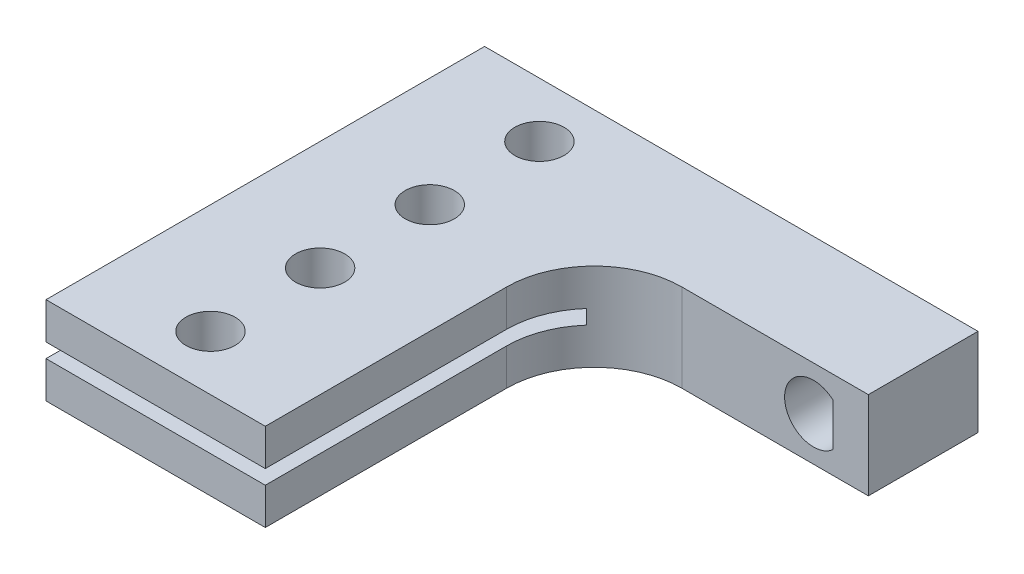
SolidWorks part; units mm, degrees
ref_plane "Front Plane" through (0, 0, 0) normal (0, 0, 1) x (1, 0, 0)
ref_plane "Top Plane" through (0, 0, 0) normal (0, 1, 0) x (1, 0, 0)
ref_plane "Right Plane" through (0, 0, 0) normal (1, 0, 0) x (0, 0, -1)
sketch "Sketch1" plane through (0, 0, 0) normal (0, 1, 0) x (1, 0, 0)
  line L0 (-33.097, 5.3879) -> (-20.397, 5.3879)
  line L2 (-20.397, 5.3879) -> (-4.522, 5.3879)
  line L3 (-4.522, 5.3879) -> (-4.522, -0.9621)
  line L4 (-4.522, -0.9621) -> (-20.397, -0.9621)
  line L5 (-20.397, -0.9621) -> (-20.397, -20.0121)
  line L6 (-20.397, -20.0121) -> (-33.097, -20.0121)
  line L7 (-33.097, -20.0121) -> (-33.097, 5.3879)
  dimension "D1" = 25.4
  dimension "D2" = 12.7
  dimension "D3" = 6.35
  dimension "D4" = 15.875
extrude "Boss-Extrude1" add sketch "Sketch1" along normal blind 5.08
sketch "Sketch2" plane through (-33.097, 0, 0) normal (-1, 0, 0) x (0, 0, 1)
  line L0 (-5.3879, 5.08) -> (-5.3879, 0) construction
  line L1 (-5.3879, 2.9567) -> (20.0121, 2.9567)
  line L2 (-5.3879, 2.9567) -> (-5.3879, 2.1233)
  line L3 (-5.3879, 2.1233) -> (20.0121, 2.1233)
  line L4 (20.0121, 2.9567) -> (20.0121, 2.1233)
  line L5 (20.0121, 5.08) -> (20.0121, 0) construction
  line L6 (7.3121, 5.08) -> (7.3121, 2.9567) construction
  line L7 (-5.3879, 5.08) -> (20.0121, 5.08) construction
  line L8 (7.3121, 2.1233) -> (7.3121, 0) construction
  line L9 (-5.3879, 0) -> (20.0121, 0) construction
  dimension "D1" = 0.8334
extrude "Cut-Extrude1" cut sketch "Sketch2" against normal blind 13.97
sketch "Sketch3" plane through (0, 5.08, 0) normal (0, 1, 0) x (1, 0, 0)
  line L0 (-33.097, 5.3879) -> (-33.097, -20.0121) construction
  line L2 (-33.097, -20.0121) -> (-20.397, -20.0121) construction
  circle A0 centre (-26.747, -16.8371) radius 1.4224
  circle A1 centre (-26.747, -10.4871) radius 1.4224
  circle A2 centre (-26.747, -4.1371) radius 1.4224
  circle A3 centre (-26.747, 2.2129) radius 1.4224
  dimension "D1" = 2.8448
  dimension "D4" = 4
  dimension "D2" = 6.35
  dimension "D3" = 3.175
  dimension "D5" = 6.35
extrude "Cut-Extrude2" cut sketch "Sketch3" against normal blind 12.7
sketch "Sketch5" plane through (0, 0, 0.9621) normal (0, 0, 1) x (1, 0, 0)
  line L0 (-4.522, 5.08) -> (-4.522, 0) construction
  line L1 (-20.397, 5.08) -> (-4.522, 5.08) construction
  line L2 (-9.3734, 2.54) -> (-9.3734, 5.4864) construction
  line L3 (-6.5794, 1.2905) -> (-6.5794, 3.7895)
  arc A0 (-6.5794, 3.7895) -> (-6.5794, 1.2905) centre (-7.697, 2.54) ccw
  dimension "D1" = 3.3528
  dimension "D2" = 3.175
  dimension "D3" = 2.54
  dimension "D4" = 2.794
extrude "Cut-Extrude3" cut sketch "Sketch5" against normal blind 12.7
fillet "Fillet3" radius 5.08 2 edges at (-20.397, 4.0184, 0.9621) (-20.397, 1.0616, 0.9621)
